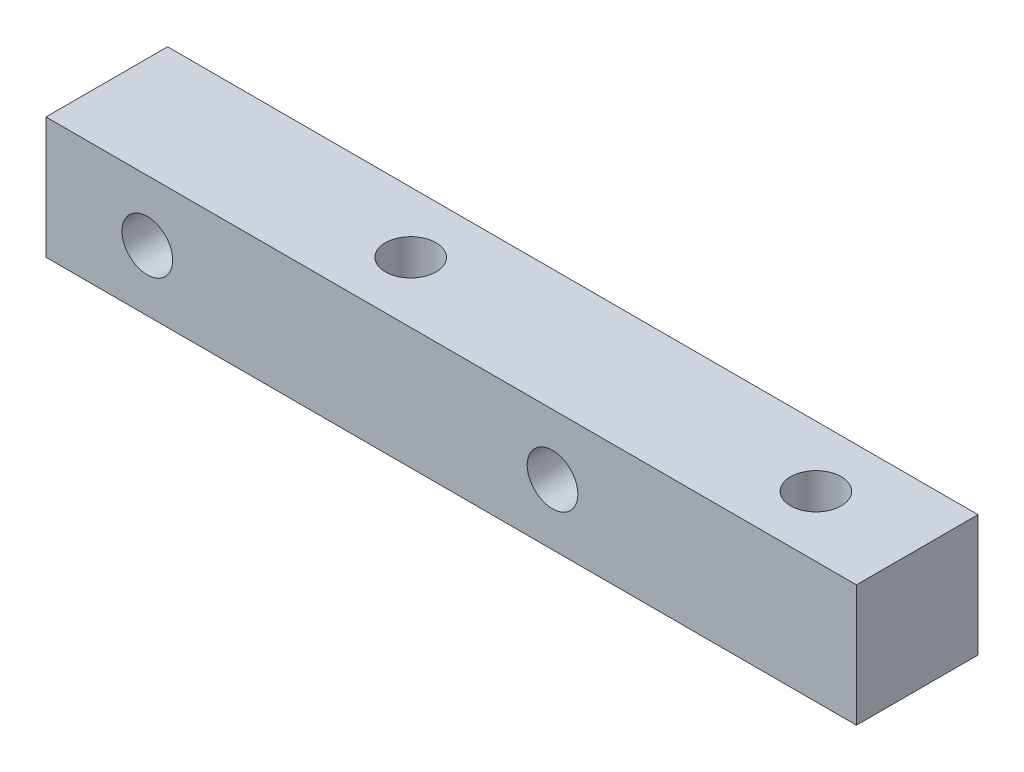
SolidWorks part; units mm, degrees
material "6063-T5"
ref_plane "前视基准面" through (0, 0, 0) normal (0, 0, 1) x (1, 0, 0)
ref_plane "上视基准面" through (0, 0, 0) normal (0, 1, 0) x (1, 0, 0)
ref_plane "右视基准面" through (0, 0, 0) normal (1, 0, 0) x (0, 0, -1)
sketch "草图1" plane through (0, 0, 0) normal (0, 1, 0) x (1, 0, 0)
  line L1 (-20, 3) -> (20, 3)
  line L2 (-20, 3) -> (-20, -3)
  line L3 (-20, -3) -> (20, -3)
  line L4 (20, 3) -> (20, -3)
  line L5 (-20, 3) -> (20, -3) construction
  line L6 (-20, -3) -> (20, 3) construction
  point P0 (0, 0)
  dimension "D1" = 6
  dimension "D2" = 40
extrude "凸台-拉伸1" add sketch "草图1" along normal mid plane 6
sketch "草图2" plane through (0, 3, 0) normal (0, 1, 0) x (1, 0, 0)
  line L0 (0, 10.9891) -> (0, -9.0892) construction
  line L1 (20, -3) -> (20, 3) construction
  circle A0 centre (-5, 0) radius 1.5
  circle A1 centre (15, 0) radius 1.5
  dimension "D1" = 10
  dimension "D2" = 3
  dimension "D3" = 5
  dimension "D4" = 3
hole_wizard "M3 螺纹孔1" positions "3D草图1" profile "草图3" tap size "M3" standard "GB" end condition through all
sketch3d "3D草图1"
  point P0 (15, 3, 0)
  point P3 (-5, 3, 0)
sketch "草图3" plane through (15, 3, 0) normal (1, 0, 0) x (0, 0, 1)
  line L0 (0, 0) -> (0, 6)
  line L1 (0, 6) -> (1.25, 6)
  line L2 (1.25, 6) -> (1.25, 0)
  line L5 (1.25, 0) -> (0, 0)
  line L11 (0, -6.35) -> (0, 107.95) construction
  dimension "通孔螺纹孔钻头直径" = 2.5
  dimension "通孔螺纹孔钻头深度" = 6
cosmetic thread "孔螺蚊线1" parameters "D2"=3
cosmetic thread "孔螺蚊线2" parameters "D2"=3
sketch "草图4" plane through (0, 0, 3) normal (0, 0, 1) x (1, 0, 0)
  line L0 (-20, 3) -> (-20, -3) construction
  circle A0 centre (5, 0) radius 1.5
  circle A1 centre (-15, 0) radius 1.5
  dimension "D1" = 5
  dimension "D2" = 3
  dimension "D3" = 3
  dimension "D4" = 20
hole_wizard "M3 螺纹孔2" positions "3D草图2" profile "草图5" tap size "M3" standard "GB" end condition through all
sketch3d "3D草图2"
  point P0 (-15, 0, 3)
  point P3 (5, 0, 3)
sketch "草图5" plane through (-15, 0, 3) normal (1, 0, 0) x (0, -1, 0)
  line L0 (0, 0) -> (0, 6)
  line L1 (0, 6) -> (1.25, 6)
  line L2 (1.25, 6) -> (1.25, 0)
  line L5 (1.25, 0) -> (0, 0)
  line L11 (0, -6.35) -> (0, 107.95) construction
  dimension "通孔螺纹孔钻头直径" = 2.5
  dimension "通孔螺纹孔钻头深度" = 6
cosmetic thread "孔螺蚊线3" parameters "D2"=3
cosmetic thread "孔螺蚊线4" parameters "D2"=3
